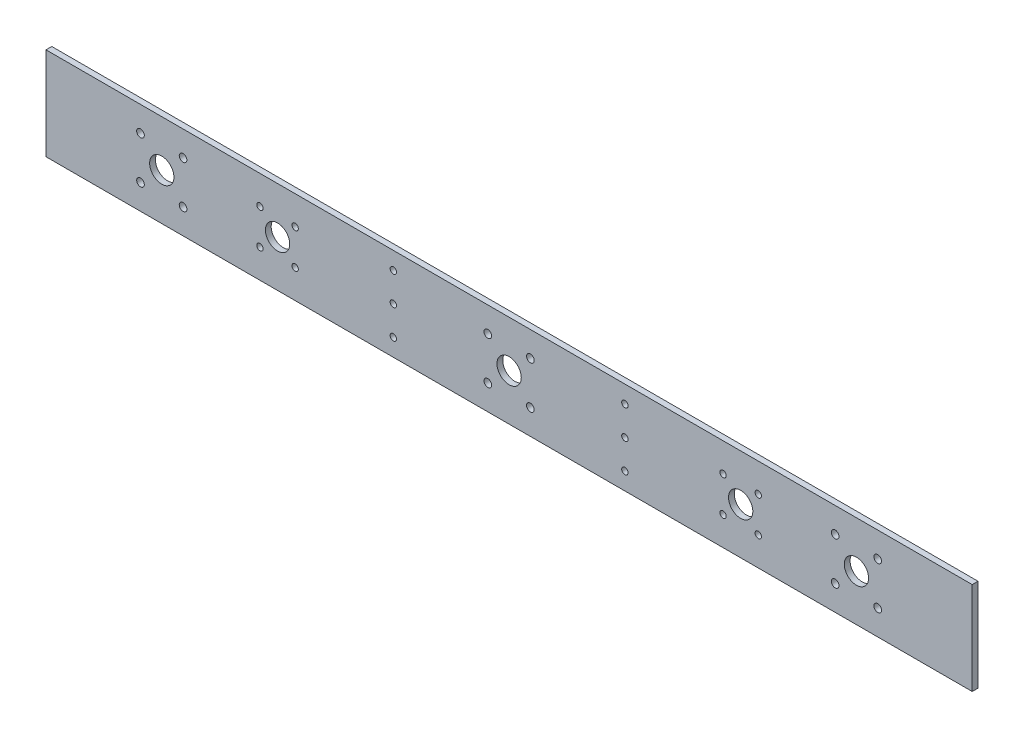
SolidWorks part; units mm, degrees
ref_plane "前视基准面" through (0, 0, 0) normal (0, 0, 1) x (1, 0, 0)
ref_plane "上视基准面" through (0, 0, 0) normal (0, 1, 0) x (1, 0, 0)
ref_plane "右视基准面" through (0, 0, 0) normal (1, 0, 0) x (0, 0, -1)
sketch "草图1" plane through (0, 0, 0) normal (0, 0, 1) x (1, 0, 0)
  line L0 (0, 40) -> (0, 0) construction
  line L1 (400, -40) -> (-400, -40)
  line L2 (400, -40) -> (400, 40)
  line L3 (400, 40) -> (-400, 40)
  line L4 (-400, -40) -> (-400, 40)
  line L5 (400, -40) -> (-400, 40) construction
  line L6 (400, 40) -> (-400, -40) construction
  line L7 (0, 0) -> (-400, 0) construction
  line L9 (-281.6152, -18.3848) -> (-318.3848, -18.3848) construction
  line L10 (-281.6152, -18.3848) -> (-281.6152, 18.3848) construction
  line L11 (-281.6152, 18.3848) -> (-318.3848, 18.3848) construction
  line L12 (-318.3848, -18.3848) -> (-318.3848, 18.3848) construction
  line L13 (-281.6152, -18.3848) -> (-318.3848, 18.3848) construction
  line L14 (-281.6152, 18.3848) -> (-318.3848, -18.3848) construction
  line L15 (-184.7972, -15.2028) -> (-215.2028, -15.2028) construction
  line L16 (-184.7972, -15.2028) -> (-184.7972, 15.2028) construction
  line L17 (-184.7972, 15.2028) -> (-215.2028, 15.2028) construction
  line L18 (-215.2028, -15.2028) -> (-215.2028, 15.2028) construction
  line L19 (-184.7972, -15.2028) -> (-215.2028, 15.2028) construction
  line L20 (-184.7972, 15.2028) -> (-215.2028, -15.2028) construction
  line L21 (18.3848, -18.3848) -> (-18.3848, -18.3848) construction
  line L22 (18.3848, -18.3848) -> (18.3848, 18.3848) construction
  line L23 (18.3848, 18.3848) -> (-18.3848, 18.3848) construction
  line L24 (-18.3848, -18.3848) -> (-18.3848, 18.3848) construction
  line L25 (18.3848, -18.3848) -> (-18.3848, 18.3848) construction
  line L26 (18.3848, 18.3848) -> (-18.3848, -18.3848) construction
  line L27 (-106.3908, -25) -> (-93.6092, -25) construction
  line L28 (-106.3908, -25) -> (-106.3908, 25) construction
  line L29 (-106.3908, 25) -> (-93.6092, 25) construction
  line L30 (-93.6092, -25) -> (-93.6092, 25) construction
  line L31 (-106.3908, -25) -> (-93.6092, 25) construction
  line L32 (-106.3908, 25) -> (-93.6092, -25) construction
  circle A0 centre (-318.3848, 18.3848) radius 3.3
  circle A1 centre (-281.6152, 18.3848) radius 3.3
  circle A2 centre (-281.6152, -18.3848) radius 3.3
  circle A3 centre (-318.3848, -18.3848) radius 3.3
  circle A4 centre (-215.2028, 15.2028) radius 2.75
  circle A5 centre (-184.7972, 15.2028) radius 2.75
  circle A6 centre (-184.7972, -15.2028) radius 2.75
  circle A7 centre (-215.2028, -15.2028) radius 2.75
  circle A8 centre (-200, 0) radius 10.5
  circle A9 centre (-18.3848, 18.3848) radius 3.3
  circle A10 centre (18.3848, 18.3848) radius 3.3
  circle A11 centre (18.3848, -18.3848) radius 3.3
  circle A12 centre (-18.3848, -18.3848) radius 3.3
  circle A13 centre (215.2028, -15.2028) radius 2.75
  circle A14 centre (184.7972, -15.2028) radius 2.75
  circle A15 centre (184.7972, 15.2028) radius 2.75
  circle A16 centre (215.2028, 15.2028) radius 2.75
  circle A17 centre (200, 0) radius 10.5
  circle A18 centre (318.3848, -18.3848) radius 3.3
  circle A19 centre (281.6152, -18.3848) radius 3.3
  circle A20 centre (281.6152, 18.3848) radius 3.3
  circle A21 centre (318.3848, 18.3848) radius 3.3
  circle A22 centre (-100, 25) radius 2.75
  circle A23 centre (-100, 0) radius 2.75
  circle A24 centre (-100, -25) radius 2.75
  circle A25 centre (100, -25) radius 2.75
  circle A26 centre (100, 0) radius 2.75
  circle A27 centre (100, 25) radius 2.75
  circle A28 centre (-300, 0) radius 10.5
  circle A29 centre (0, 0) radius 10.5
  circle A30 centre (300, 0) radius 10.5
  point P0 (0, 0)
  point P9 (-300, 0)
  point P10 (-200, 0)
  point P11 (-200, 0)
  point P12 (0, 0)
  point P14 (-300, 0)
  point P58 (-100, 0)
  dimension "D7" = 6.6
  dimension "D8" = 5.5
  dimension "D9" = 21
  dimension "D11" = 5.5
  dimension "D12" = 25
  dimension "D14" = 21
  dimension "D15" = 21
  dimension "D1" = 800
  dimension "D2" = 80
  dimension "D3" = 200
  dimension "D4" = 100
  dimension "D5" = 52
  dimension "D6" = 43
  dimension "D10" = 52
  dimension "D13" = 100
extrude "凸台-拉伸1" add sketch "草图1" along normal blind 5
